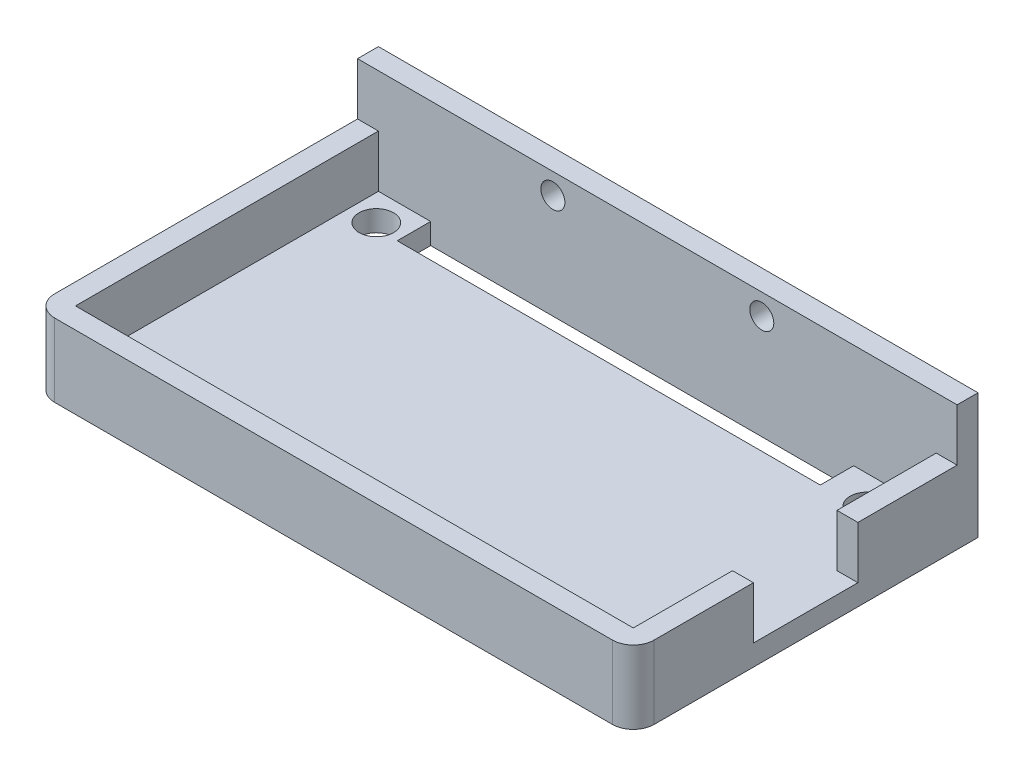
SolidWorks part; units mm, degrees
ref_plane "Front Plane" through (0, 0, 0) normal (0, 0, 1) x (1, 0, 0)
ref_plane "Top Plane" through (0, 0, 0) normal (0, 1, 0) x (1, 0, 0)
ref_plane "Right Plane" through (0, 0, 0) normal (1, 0, 0) x (0, 0, -1)
sketch "Sketch1" plane through (0, 0, 0) normal (0, 1, 0) x (1, 0, 0)
  line L1 (0, 0) -> (57.4, 0)
  line L2 (0, 0) -> (0, 33)
  line L3 (0, 33) -> (57.4, 33)
  line L4 (57.4, 0) -> (57.4, 33)
  dimension "D1" = 57.4
  dimension "D2" = 33
extrude "Boss-Extrude1" add sketch "Sketch1" along normal blind 7
shell "Shell3" thickness 2 removed face at (28.7, 7, -16.5)
sketch "Sketch2" plane through (0, 2, 0) normal (0, 1, 0) x (1, 0, 0)
  line L0 (4.5, 28.3) -> (4.5, 4.7) construction
  line L1 (2, 2) -> (2, 31) construction
  line L2 (2, 31) -> (2, 2) construction
  circle A0 centre (4.5, 28.3) radius 1.65
  circle A1 centre (51.5, 28.3) radius 1.65
  circle A2 centre (4.5, 4.7) radius 1.65
  circle A3 centre (51.5, 4.7) radius 1.65
  point P10 (2, 16.5)
  point P11 (4.5, 16.5)
  dimension "D1" = 3.3
  dimension "D2" = 47
  dimension "D3" = 23.6
  dimension "D4" = 2.5
extrude "Cut-Extrude1" cut sketch "Sketch2" against normal through all
sketch "Sketch3" plane through (0, 2, 0) normal (0, 1, 0) x (1, 0, 0)
  line L0 (55.4, 31) -> (2, 31) construction
  line L1 (7, 31) -> (47.5, 31)
  line L2 (7, 31) -> (7, 27.8)
  line L3 (7, 27.8) -> (47.5, 27.8)
  line L4 (47.5, 31) -> (47.5, 27.8)
  line L5 (2, 31) -> (2, 2) construction
  line L6 (2, 16.5) -> (55.4, 16.5) construction
  line L7 (55.4, 2) -> (55.4, 31) construction
  line L8 (47.5, 2) -> (47.5, 5.2)
  line L9 (7, 5.2) -> (47.5, 5.2)
  line L10 (7, 2) -> (7, 5.2)
  line L11 (7, 2) -> (47.5, 2)
  circle A0 centre (51.5, 28.3) radius 1.65 construction
  dimension "D1" = 5
  dimension "D2" = 4
  dimension "D3" = 3.2
extrude "Cut-Extrude2" cut sketch "Sketch3" against normal through all
sketch "Sketch4" plane through (0, 7, 0) normal (0, 1, 0) x (1, 0, 0)
  line L0 (55.4, 2) -> (55.4, 31) construction
  line L1 (55.4, 21.5) -> (57.4, 21.5)
  line L2 (55.4, 21.5) -> (55.4, 11.5)
  line L3 (55.4, 11.5) -> (57.4, 11.5)
  line L4 (57.4, 21.5) -> (57.4, 11.5)
  line L5 (57.4, 0) -> (57.4, 33) construction
  point P8 (57.4, 16.5)
  point P9 (57.4, 16.5)
  dimension "D1" = 10
extrude "Cut-Extrude3" cut sketch "Sketch4" against normal up to surface (5 mm away) up to face at (51.5, 2, -26.65)
sketch "Sketch5" plane through (0, 7, 0) normal (0, 1, 0) x (1, 0, 0)
  line L0 (57.4, 21.5) -> (57.4, 33) construction
  line L1 (0, 33) -> (57.4, 33)
  line L2 (0, 33) -> (0, 31)
  line L3 (0, 31) -> (57.4, 31)
  line L4 (57.4, 33) -> (57.4, 31)
  line L5 (55.4, 31) -> (47.5, 31) construction
extrude "Boss-Extrude2" add sketch "Sketch5" along normal blind 5
sketch "Sketch6" plane through (0, 0, -33) normal (0, 0, -1) x (-1, 0, 0)
  line L0 (-38.7, 10) -> (-18.7, 10) construction
  line L3 (-57.4, 12) -> (0, 12) construction
  circle A0 centre (-38.7, 10) radius 1.15
  circle A1 centre (-18.7, 10) radius 1.15
  point P5 (-28.7, 10)
  point P8 (-28.7, 12)
  dimension "D1" = 2.3
  dimension "D2" = 2.3
  dimension "D3" = 2
  dimension "D4" = 20
extrude "Cut-Extrude4" cut sketch "Sketch6" against normal up to next
fillet "Fillet1" radius 2 2 edges at (0, 3.5, 0) (57.4, 3.5, 0)
